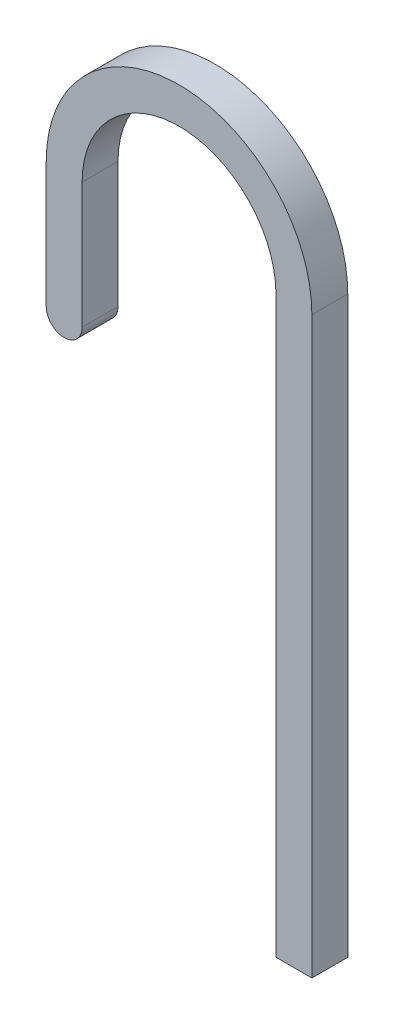
SolidWorks part; units mm, degrees
ref_plane "Front Plane" through (0, 0, 0) normal (0, 0, 1) x (1, 0, 0)
ref_plane "Top Plane" through (0, 0, 0) normal (0, 1, 0) x (1, 0, 0)
ref_plane "Right Plane" through (0, 0, 0) normal (1, 0, 0) x (0, 0, -1)
sketch "Sketch5" plane through (0, 0, 0) normal (0, 0, 1) x (1, 0, 0)
  line L0 (0, 0) -> (12.7, 0)
  line L1 (12.7, 0) -> (12.7, 203.2)
  line L2 (0, 0) -> (0, 203.2)
  line L4 (-81.28, 203.2) -> (-81.28, 152.4)
  line L5 (-81.28, 152.4) -> (-68.58, 152.4)
  line L6 (-68.58, 152.4) -> (-68.58, 203.2)
  arc A0 (0, 203.2) -> (-68.58, 203.2) centre (-34.29, 203.2) ccw
  arc A1 (12.7, 203.2) -> (-81.28, 203.2) centre (-34.29, 203.2) ccw
  dimension "D1" = 34.29
  dimension "D2" = 12.7
  dimension "D3" = 50.8
  dimension "D4" = 203.2
extrude "Boss-Extrude1" add sketch "Sketch5" along normal blind 12.7 contours A0 L6 L5 L4 A1 L1 L0 L2
fillet "Fillet3" radius 6.35 1 edges at (-68.58, 152.4, 6.35) type face fillet first side face at (-74.93, 152.4, 6.35) second side face at (-68.58, 177.8, 6.35)
fillet "Fillet4" radius 6.35 1 edges at (-81.28, 152.4, 6.35) type face fillet first side face at (-78.105, 152.4, 6.35) second side face at (-81.28, 177.8, 6.35)
